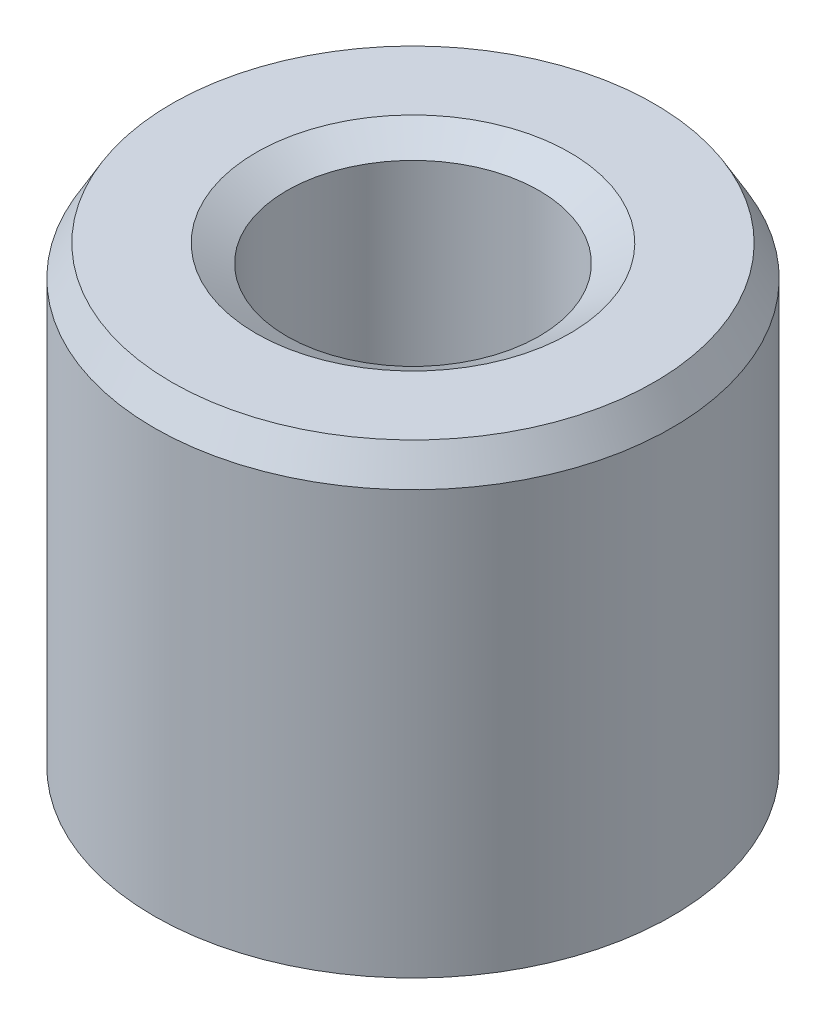
SolidWorks part; units mm, degrees
ref_plane "Front Plane" through (0, 0, 0) normal (0, 0, 1) x (1, 0, 0)
ref_plane "Top Plane" through (0, 0, 0) normal (0, 1, 0) x (1, 0, 0)
ref_plane "Right Plane" through (0, 0, 0) normal (1, 0, 0) x (0, 0, -1)
sketch "Sketch1" plane through (0, 0, 0) normal (0, 1, 0) x (1, 0, 0)
  circle A0 centre (0, 0) radius 22.5
  dimension "SLEEVE_OD" = 45
extrude "Boss-Extrude1" add sketch "Sketch1" along normal blind 40.9387
sketch "Sketch2" plane through (0, 0, 0) normal (0, 1, 0) x (1, 0, 0)
  circle A0 centre (0, 0) radius 10.9663
  dimension "BORE_D" = 21.9327
extrude "Cut-Extrude1" cut sketch "Sketch2" along normal through all
chamfer "Chamfer1" distance 2.662 angle 30 4 edges at (0, 40.9387, 10.9663) (0, 0, 10.9663) (0, 0, 22.5) (0, 40.9387, 22.5) first distance on face at (0, 40.9387, 10.9663) first distance on face at (0, 0, 10.9663) first distance on face at (0, 40.9387, 22.5)
